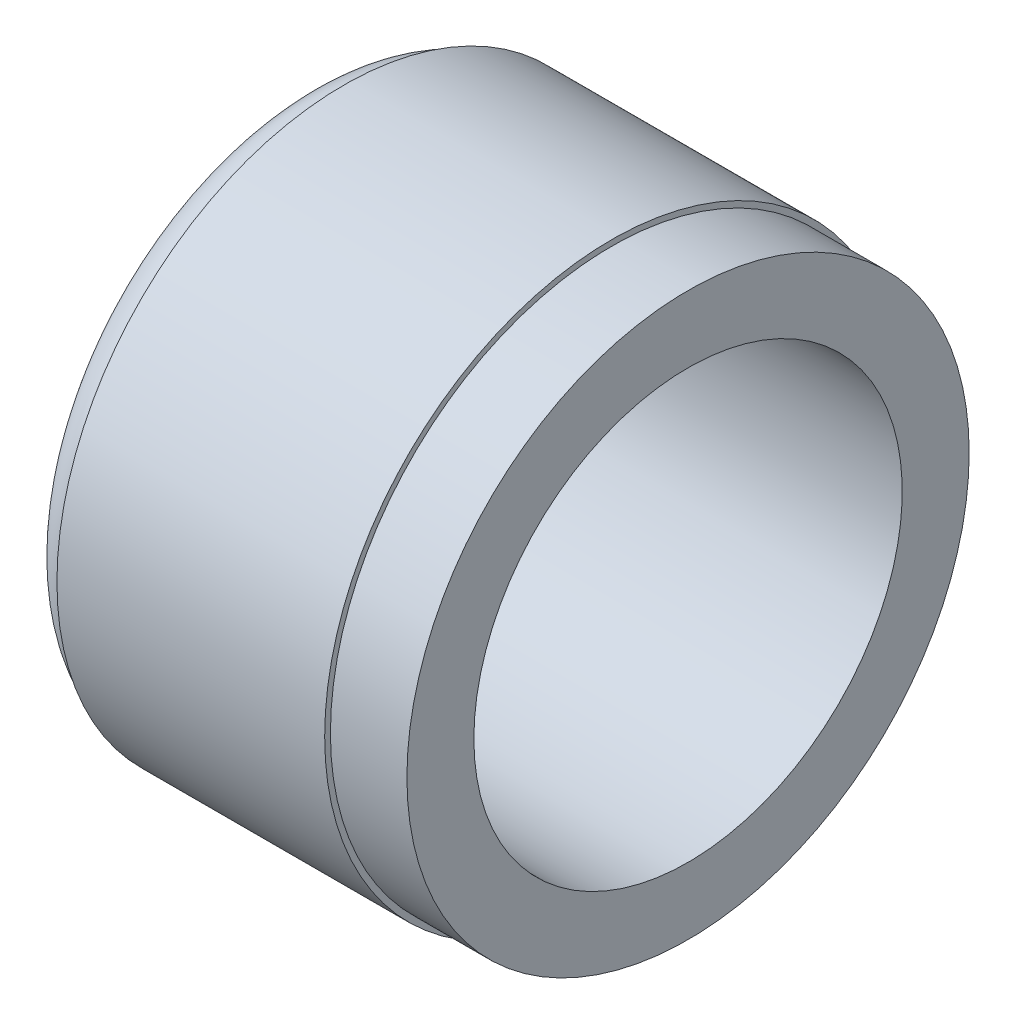
SolidWorks part; units mm, degrees
material "ABS"
ref_plane "Спереди" through (0, 0, 0) normal (0, 0, 1) x (1, 0, 0)
ref_plane "Сверху" through (0, 0, 0) normal (0, 1, 0) x (1, 0, 0)
ref_plane "Справа" through (0, 0, 0) normal (1, 0, 0) x (0, 0, -1)
sketch "Эскиз1" plane through (0, 0, 0) normal (0, 0, 1) x (1, 0, 0)
  line L0 (0, 0) -> (88.0157, 0) construction
  line L1 (0, 11.2) -> (20, 11.2)
  line L2 (20, 11.2) -> (20, 14.7)
  line L3 (20, 14.7) -> (16, 14.7)
  line L4 (16, 14.7) -> (16, 15)
  line L5 (16, 15) -> (2, 15)
  line L6 (2, 15) -> (2, 14.7)
  line L7 (2, 14.7) -> (0, 14.7)
  line L8 (0, 11.2) -> (0, 14.7)
  dimension "D1" = 20
  dimension "D2" = 30
  dimension "D3" = 4
  dimension "D4" = 2
  dimension "D5" = 0.3
  dimension "D6" = 22.4
revolve "Повернуть1" add sketch "Эскиз1" angle 360 about L0
fillet "Скругление1" radius 2 1 edges at (0, 0, 14.7)
